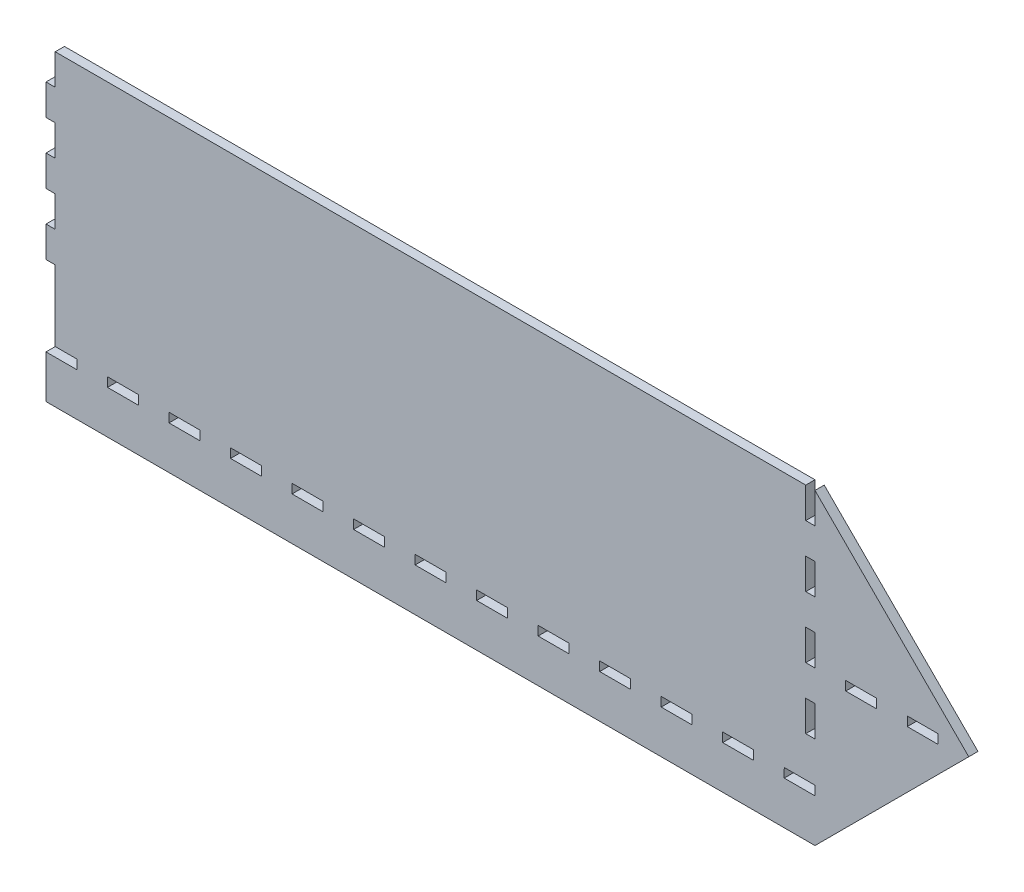
SolidWorks part; units mm, degrees
ref_plane "Front Plane" through (0, 0, 0) normal (0, 0, 1) x (1, 0, 0)
ref_plane "Top Plane" through (0, 0, 0) normal (0, 1, 0) x (1, 0, 0)
ref_plane "Right Plane" through (0, 0, 0) normal (1, 0, 0) x (0, 0, -1)
sketch "Sketch1" plane through (0, 0, 0) normal (0, 0, 1) x (1, 0, 0)
  line L0 (-112.631, -67.7284) -> (-112.631, -53.7284)
  line L2 (-72.631, -50.7284) -> (-62.631, -50.7284)
  line L3 (-62.631, 32.2716) -> (137.369, 32.2716)
  line L4 (137.369, 32.2716) -> (187.369, -17.7284)
  line L5 (187.369, -17.7284) -> (137.369, -67.7284)
  line L6 (137.369, -67.7284) -> (-112.631, -67.7284)
  line L9 (137.369, 32.2716) -> (137.369, -67.7284) construction
  line L10 (137.369, -17.7284) -> (187.369, -17.7284) construction
  line L11 (157.369, -16.2284) -> (147.369, -16.2284)
  line L12 (177.369, -16.2284) -> (167.369, -16.2284)
  line L13 (177.369, -16.2284) -> (177.369, -19.2284)
  line L14 (177.369, -19.2284) -> (167.369, -19.2284)
  line L15 (167.369, -16.2284) -> (167.369, -19.2284)
  line L16 (177.369, -16.2284) -> (167.369, -19.2284) construction
  line L17 (177.369, -19.2284) -> (167.369, -16.2284) construction
  line L18 (157.369, -16.2284) -> (157.369, -19.2284)
  line L19 (157.369, -19.2284) -> (147.369, -19.2284)
  line L20 (147.369, -16.2284) -> (147.369, -19.2284)
  line L21 (137.3812, -50.7284) -> (127.3812, -50.7284)
  line L22 (137.3812, -50.7284) -> (137.3692, -53.7284)
  line L23 (137.3692, -53.7284) -> (127.3692, -53.7284)
  line L24 (127.3812, -50.7284) -> (127.3692, -53.7284)
  line L25 (137.3812, -50.7284) -> (127.3692, -53.7284) construction
  line L26 (137.3692, -53.7284) -> (127.3812, -50.7284) construction
  line L27 (117.3811, -50.7284) -> (107.3787, -50.7284)
  line L28 (117.3811, -50.7284) -> (117.3691, -53.7284)
  line L29 (117.3691, -53.7284) -> (107.3691, -53.7284)
  line L30 (107.3787, -50.7284) -> (107.3691, -53.7284)
  line L31 (117.3811, -50.7284) -> (107.3691, -53.7284) construction
  line L32 (117.3691, -53.7284) -> (107.3787, -50.7284) construction
  line L33 (97.3787, -50.7284) -> (87.3763, -50.7284)
  line L34 (97.3787, -50.7284) -> (97.369, -53.7284)
  line L35 (97.369, -53.7284) -> (87.369, -53.7284)
  line L36 (87.3763, -50.7284) -> (87.369, -53.7284)
  line L37 (97.3787, -50.7284) -> (87.369, -53.7284) construction
  line L38 (97.369, -53.7284) -> (87.3763, -50.7284) construction
  line L39 (77.3763, -50.7284) -> (67.3738, -50.7284)
  line L40 (77.3763, -50.7284) -> (77.369, -53.7284)
  line L41 (77.369, -53.7284) -> (67.369, -53.7284)
  line L42 (67.3738, -50.7284) -> (67.369, -53.7284)
  line L43 (77.3763, -50.7284) -> (67.369, -53.7284) construction
  line L44 (77.369, -53.7284) -> (67.3738, -50.7284) construction
  line L45 (57.3738, -50.7284) -> (47.3714, -50.7284)
  line L46 (57.3738, -50.7284) -> (57.369, -53.7284)
  line L47 (57.369, -53.7284) -> (47.369, -53.7284)
  line L48 (47.3714, -50.7284) -> (47.369, -53.7284)
  line L49 (57.3738, -50.7284) -> (47.369, -53.7284) construction
  line L50 (57.369, -53.7284) -> (47.3714, -50.7284) construction
  line L51 (37.3714, -50.7284) -> (27.369, -50.7284)
  line L52 (37.3714, -50.7284) -> (37.369, -53.7284)
  line L53 (37.369, -53.7284) -> (27.369, -53.7284)
  line L54 (27.369, -50.7284) -> (27.369, -53.7284)
  line L55 (37.3714, -50.7284) -> (27.369, -53.7284) construction
  line L56 (37.369, -53.7284) -> (27.369, -50.7284) construction
  line L57 (17.369, -50.7284) -> (7.369, -50.7284)
  line L58 (17.369, -50.7284) -> (17.369, -53.7284)
  line L59 (17.369, -53.7284) -> (7.369, -53.7284)
  line L60 (7.369, -50.7284) -> (7.369, -53.7284)
  line L61 (17.369, -50.7284) -> (7.369, -53.7284) construction
  line L62 (17.369, -53.7284) -> (7.369, -50.7284) construction
  line L63 (-2.631, -50.7284) -> (-12.631, -50.7284)
  line L64 (-2.631, -50.7284) -> (-2.631, -53.7284)
  line L65 (-2.631, -53.7284) -> (-12.631, -53.7284)
  line L66 (-12.631, -50.7284) -> (-12.631, -53.7284)
  line L67 (-2.631, -50.7284) -> (-12.631, -53.7284) construction
  line L68 (-2.631, -53.7284) -> (-12.631, -50.7284) construction
  line L69 (-22.631, -50.7284) -> (-32.631, -50.7284)
  line L70 (-22.631, -50.7284) -> (-22.631, -53.7284)
  line L71 (-22.631, -53.7284) -> (-32.631, -53.7284)
  line L72 (-32.631, -50.7284) -> (-32.631, -53.7284)
  line L73 (-22.631, -50.7284) -> (-32.631, -53.7284) construction
  line L74 (-22.631, -53.7284) -> (-32.631, -50.7284) construction
  line L75 (-42.631, -50.7284) -> (-52.631, -50.7284)
  line L76 (-42.631, -50.7284) -> (-42.631, -53.7284)
  line L77 (-42.631, -53.7284) -> (-52.631, -53.7284)
  line L78 (-52.631, -50.7284) -> (-52.631, -53.7284)
  line L79 (-42.631, -50.7284) -> (-52.631, -53.7284) construction
  line L80 (-42.631, -53.7284) -> (-52.631, -50.7284) construction
  line L82 (-62.631, -50.7284) -> (-62.631, -53.7284)
  line L83 (-62.631, -53.7284) -> (-72.631, -53.7284)
  line L84 (-72.631, -50.7284) -> (-72.631, -53.7284)
  line L85 (-62.631, -50.7284) -> (-72.631, -53.7284) construction
  line L86 (-62.631, -53.7284) -> (-72.631, -50.7284) construction
  line L87 (137.369, 12.2716) -> (134.369, 12.2716)
  line L88 (-82.631, -50.7284) -> (-82.631, -53.7284)
  line L89 (-82.631, -53.7284) -> (-92.631, -53.7284)
  line L90 (-92.631, -50.7284) -> (-92.631, -53.7284)
  line L91 (-82.631, -50.7284) -> (-92.631, -53.7284) construction
  line L92 (-82.631, -53.7284) -> (-92.631, -50.7284) construction
  line L93 (137.369, 32.2716) -> (134.369, 32.2716)
  line L94 (-102.631, -50.7284) -> (-102.631, -53.7284)
  line L95 (-102.631, -53.7284) -> (-112.631, -53.7284)
  line L97 (-102.631, -50.7284) -> (-112.631, -53.7284) construction
  line L98 (-102.631, -53.7284) -> (-107.631, -52.2284) construction
  line L99 (-62.631, -50.7284) -> (-72.631, -50.7284) [skipped]
  line L100 (-82.631, -50.7284) -> (-92.631, -50.7284) [skipped]
  line L101 (-102.631, -50.7284) -> (-112.631, -50.7284) [skipped]
  line L102 (137.369, 32.2716) -> (137.369, 22.2716)
  line L103 (137.369, 22.2716) -> (134.369, 22.2716)
  line L104 (134.369, 32.2716) -> (134.369, 22.2716)
  line L105 (137.369, 12.2716) -> (137.369, 2.2716)
  line L106 (137.369, 2.2716) -> (134.369, 2.2716)
  line L107 (134.369, 12.2716) -> (134.369, 2.2716)
  line L108 (137.369, -7.7284) -> (134.369, -7.7284)
  line L109 (137.369, -7.7284) -> (137.369, -17.7284)
  line L111 (137.369, -17.7284) -> (134.369, -17.7284)
  line L114 (157.369, -16.2284) -> (147.369, -19.2284) construction
  line L121 (134.369, -7.7284) -> (134.369, -17.7284)
  line L122 (157.369, -19.2284) -> (147.369, -16.2284) construction
  line L124 (-109.631, -50.7284) -> (-102.631, -50.7284)
  line L125 (-112.631, -52.2284) -> (-112.631, -53.3547) [skipped]
  line L126 (-62.631, 32.2716) -> (-109.631, 32.2716)
  line L127 (-112.631, -7.7284) -> (-109.631, -7.7284)
  line L128 (137.369, -27.7284) -> (134.369, -27.7284)
  line L129 (137.369, -27.7284) -> (137.369, -37.7284)
  line L130 (137.369, -37.7284) -> (134.369, -37.7284)
  line L131 (134.369, -27.7284) -> (134.369, -37.7284)
  line L132 (-112.631, 22.2716) -> (-112.631, 12.2716)
  line L133 (-109.631, -17.7284) -> (-112.631, -17.7284)
  line L134 (-112.631, -27.7284) -> (-109.631, -27.7284)
  line L135 (-109.631, -50.7284) -> (-109.631, -27.7284)
  line L136 (-109.631, 2.2716) -> (-112.631, 2.2716)
  line L137 (-112.631, 2.2716) -> (-112.631, -7.7284)
  line L138 (-109.631, 22.2716) -> (-109.631, 32.2716)
  line L139 (-109.631, 22.2716) -> (-112.631, 22.2716)
  line L140 (-112.631, 12.2716) -> (-109.631, 12.2716)
  line L141 (-109.631, -17.7284) -> (-109.631, -7.7284)
  line L142 (-112.631, -17.7284) -> (-112.631, -27.7284)
  line L143 (-109.631, 2.2716) -> (-109.631, 12.2716)
  line L144 (-92.631, -50.7284) -> (-82.631, -50.7284)
  point P5 (172.369, -17.7284)
  point P9 (151.1235, -51.5486)
  point P17 (152.369, -17.7284)
  point P19 (131.1235, -51.6165)
  point P24 (111.1235, -51.6845)
  point P29 (91.1235, -51.7525)
  point P34 (71.1235, -51.8205)
  point P39 (51.1235, -51.8885)
  point P44 (31.1235, -51.9564)
  point P49 (11.1235, -52.0244)
  point P54 (-8.8765, -52.0924)
  point P59 (-28.8765, -52.1604)
  point P64 (-48.8765, -52.2284)
  point P70 (-68.8765, -52.2284)
  point P75 (-88.8765, -52.2284)
  point P80 (-108.8765, -52.2284)
  dimension "D1" = 100
  dimension "D3" = 300
  dimension "D5" = 50
  dimension "D6" = 10
  dimension "D7" = 10
  dimension "D8" = 10
  dimension "D10" = 3
  dimension "D11" = 14
  dimension "D13" = 3
  dimension "D14" = 10
  dimension "D21" = 10
  dimension "D22" = 10
  dimension "D23" = 10
  dimension "D24" = 10
  dimension "D25" = 10
  dimension "D26" = 10
  dimension "D9" = 10
  dimension "D27" = 10
  dimension "D28" = 10
  dimension "D29" = 10
  dimension "D30" = 10
  dimension "D31" = 10
  dimension "D32" = 10
  dimension "D33" = 10
  dimension "D34" = 10
  dimension "D35" = 10
  dimension "D36" = 10
  dimension "D37" = 10
  dimension "D38" = 10
  dimension "D39" = 10
  dimension "D40" = 3
  dimension "D41" = 10
  dimension "D20" = 47
  dimension "D42" = 3
  dimension "D12" = 4
  dimension "D16" = 4
extrude "Boss-Extrude1" add sketch "Sketch1" along normal blind 3 contours L94 L95 L0 L6 L5 L4 L3 L82 L83 L84 L88 L89 L90 L24 L21 L22 L23 L30 L27 L28 L29 L36 L33 L34 L35 L42 L39 L40 L41 L48 L45 L46 L47 region at (25.4421, -17.3216, 0)
